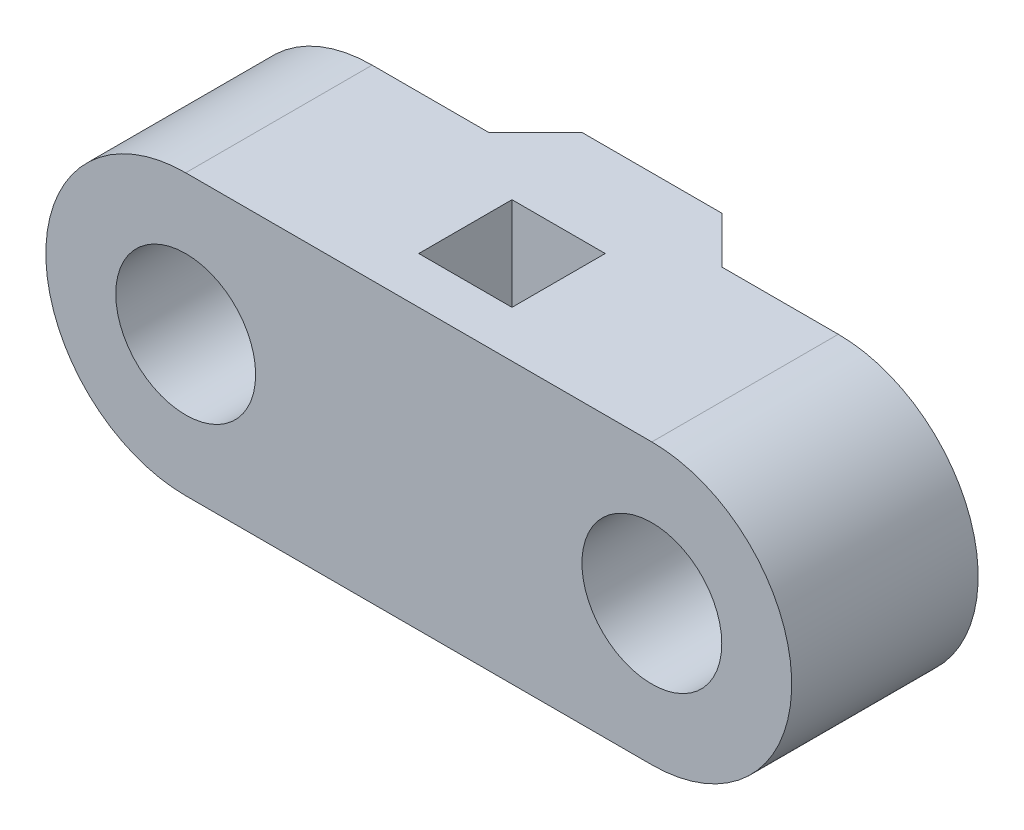
SolidWorks part; units mm, degrees
ref_plane "Front Plane" through (0, 0, 0) normal (0, 0, 1) x (1, 0, 0)
ref_plane "Top Plane" through (0, 0, 0) normal (0, 1, 0) x (1, 0, 0)
ref_plane "Right Plane" through (0, 0, 0) normal (1, 0, 0) x (0, 0, -1)
sketch "Sketch1" plane through (0, 0, 0) normal (0, 1, 0) x (1, 0, 0)
  line L0 (0, 50.8264) -> (0, -46.0331) construction
  line L1 (-87.1092, 0) -> (82.7633, 0) construction
  line L2 (-15, 30) -> (15, 30)
  line L3 (10, -10) -> (-10, -10)
  line L4 (10, -10) -> (10, 10)
  line L5 (10, 10) -> (-10, 10)
  line L6 (-10, -10) -> (-10, 10)
  line L7 (10, -10) -> (-10, 10) construction
  line L8 (10, 10) -> (-10, -10) construction
  line L9 (15, 30) -> (15, 20)
  line L10 (15, 20) -> (80, 20)
  line L11 (80, 20) -> (80, -20)
  line L17 (-80, 20) -> (-80, -20)
  line L18 (-15, 20) -> (-80, 20)
  line L19 (-15, 30) -> (-15, 20)
  line L20 (-80, -20) -> (80, -20)
  point P5 (0, 0)
  point P17 (80, 0)
  point P21 (0, -30)
  point P26 (0, 30)
  dimension "D1" = 20
  dimension "D2" = 20
  dimension "D3" = 80
  dimension "D4" = 65
  dimension "D5" = 20
  dimension "D6" = 20
extrude "Boss-Extrude1" add sketch "Sketch1" along normal blind 60
sketch "Sketch2" plane through (0, 0, 0) normal (0, 0, 1) x (1, 0, 0)
  line L0 (0, 74.6421) -> (0, -18.7606) construction
  line L1 (-50, 71.259) -> (-50, -4.6399) construction
  line L2 (-50, 60) -> (-50, 75.5246)
  line L3 (-50, 75.5246) -> (-102.6695, 75.5246)
  line L4 (-102.6695, 75.5246) -> (-102.6695, -8.4643)
  line L5 (-102.6695, -8.4643) -> (-50, -8.4643)
  line L6 (-50, -8.4643) -> (-50, 0)
  line L7 (102.6695, -8.4643) -> (50, -8.4643)
  line L8 (102.6695, 75.5246) -> (102.6695, -8.4643)
  line L9 (50, 75.5246) -> (102.6695, 75.5246)
  line L10 (50, 60) -> (50, 75.5246)
  line L11 (50, -8.4643) -> (50, 0)
  circle A0 centre (50, 30) radius 15
  circle A1 centre (-50, 30) radius 15
  arc A2 (-50, 60) -> (-50, 0) centre (-50, 30) ccw
  arc A3 (50, 60) -> (50, 0) centre (50, 30) cw
  dimension "D1" = 30
  dimension "D2" = 50
  dimension "D3" = 30
  dimension "D4" = 60
extrude "Cut-Extrude1" cut sketch "Sketch2" against normal through all both and the other way through all
chamfer "Chamfer2" distance 10 2 edges at (15, 30, -20) (-15, 30, -20)
